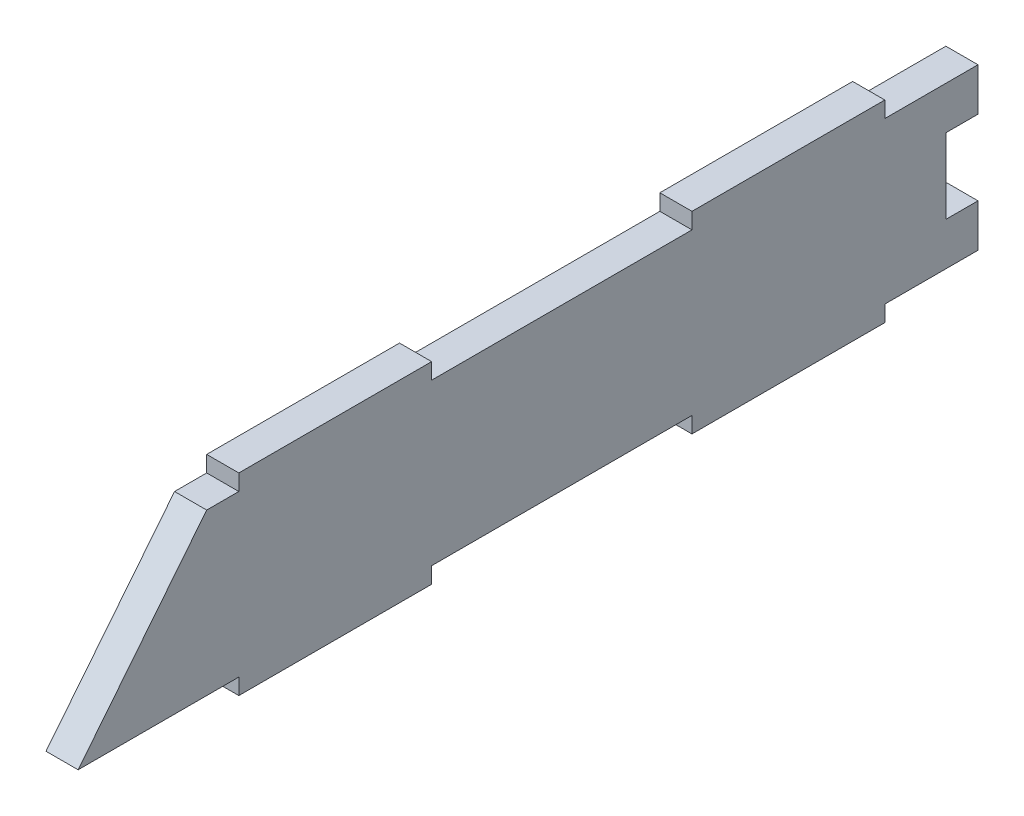
SolidWorks part; units mm, degrees
ref_plane "Front Plane" through (0, 0, 0) normal (0, 0, 1) x (1, 0, 0)
ref_plane "Top Plane" through (0, 0, 0) normal (0, 1, 0) x (1, 0, 0)
ref_plane "Right Plane" through (0, 0, 0) normal (1, 0, 0) x (0, 0, -1)
sketch "Sketch1" plane through (0, 0, 0) normal (1, 0, 0) x (0, 0, -1)
  line L1 (-177.8, -31.75) -> (177.8, -31.75)
  line L2 (-177.8, -31.75) -> (-177.8, 31.75)
  line L3 (-177.8, 31.75) -> (177.8, 31.75)
  line L4 (177.8, -31.75) -> (177.8, 31.75)
  line L5 (-177.8, -31.75) -> (177.8, 31.75) construction
  line L6 (-177.8, 31.75) -> (177.8, -31.75) construction
  point P0 (0, 0)
  dimension "D1" = 355.6
  dimension "D2" = 63.5
extrude "Boss-Extrude1" add sketch "Sketch1" along normal blind 12.7
sketch "Sketch2" plane through (12.7, 0, 0) normal (1, 0, 0) x (0, 0, -1)
  line L0 (-177.8, -31.75) -> (-127, 31.75)
  line L1 (177.8, 31.75) -> (-177.8, 31.75) construction
  dimension "D1" = 50.8
extrude "Cut-Extrude1" cut sketch "Sketch2" against normal through all and the other way through all
sketch "Sketch3" plane through (0, 0, 0) normal (-1, 0, 0) x (0, 0, 1)
  line L0 (177.8, -31.75) -> (-177.8, -31.75) construction
  line L1 (-140.97, -31.75) -> (-64.77, -31.75)
  line L2 (-140.97, -31.75) -> (-140.97, -38.1)
  line L3 (-140.97, -38.1) -> (-64.77, -38.1)
  line L4 (-64.77, -31.75) -> (-64.77, -38.1)
  line L5 (-177.8, -31.75) -> (-177.8, 31.75) construction
  line L6 (38.1, -31.75) -> (114.3, -31.75)
  line L7 (38.1, -31.75) -> (38.1, -38.1)
  line L8 (38.1, -38.1) -> (114.3, -38.1)
  line L9 (114.3, -31.75) -> (114.3, -38.1)
  line L10 (-177.8, 31.75) -> (127, 31.75) construction
  line L11 (-140.97, 31.75) -> (-64.77, 31.75)
  line L12 (-140.97, 31.75) -> (-140.97, 38.1)
  line L13 (-140.97, 38.1) -> (-64.77, 38.1)
  line L14 (-64.77, 31.75) -> (-64.77, 38.1)
  line L16 (38.1, 31.75) -> (114.3, 31.75)
  line L17 (38.1, 31.75) -> (38.1, 38.1)
  line L18 (38.1, 38.1) -> (114.3, 38.1)
  line L19 (114.3, 31.75) -> (114.3, 38.1)
  dimension "D1" = 76.2
  dimension "D2" = 6.35
  dimension "D3" = 76.2
  dimension "D4" = 6.35
  dimension "D5" = 36.83
  dimension "D6" = 215.9
  dimension "D7" = 76.2
  dimension "D8" = 6.35
  dimension "D9" = 6.35
  dimension "D10" = 76.2
extrude "Boss-Extrude2" add sketch "Sketch3" against normal blind 12.7
sketch "Sketch4" plane through (0, 0, 0) normal (-1, 0, 0) x (0, 0, 1)
  line L0 (-177.8, -31.75) -> (-177.8, 31.75) construction
  line L1 (-177.8, 14.8167) -> (-165.1, 14.8167)
  line L2 (-177.8, 14.8167) -> (-177.8, -14.8167)
  line L3 (-177.8, -14.8167) -> (-165.1, -14.8167)
  line L4 (-165.1, 14.8167) -> (-165.1, -14.8167)
  line L5 (-140.97, -31.75) -> (-177.8, -31.75) construction
  line L6 (-177.8, 31.75) -> (-140.97, 31.75) construction
  dimension "D1" = 16.9333
  dimension "D2" = 16.9333
  dimension "D3" = 12.7
extrude "Cut-Extrude2" cut sketch "Sketch4" against normal through all
